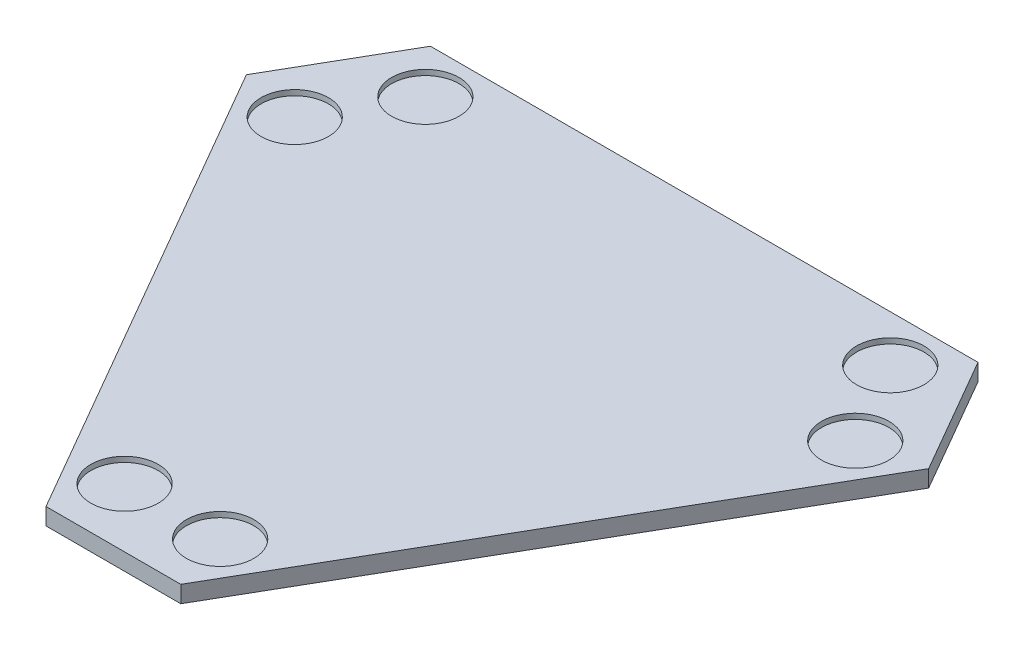
SolidWorks part; units mm, degrees
note: '?' marks a value the reader was unsure of. The reader was unsure of these and kept them because the rebuilt part matched: shared geometry of "Sketch1<5>".
ref_plane "Front Plane" through (0, 0, 0) normal (0, 0, 1) x (1, 0, 0)
ref_plane "Top Plane" through (0, 0, 0) normal (0, 1, 0) x (1, 0, 0)
ref_plane "Right Plane" through (0, 0, 0) normal (1, 0, 0) x (0, 0, -1)
sketch "Sketch1" plane through (0, 0, 0) normal (0, 1, 0) x (1, 0, 0)
  line L0 (121.2436, 70) -> (0, -140)
  line L1 (0, -140) -> (-121.2436, 70)
  line L2 (-121.2436, 70) -> (121.2436, 70)
  line L3 (121.2436, 70) -> (-60.6218, -35) construction
  line L4 (-121.2436, 70) -> (60.6218, -35) construction
  line L5 (-337.0463, -245.6128) -> (-234.4722, -67.9492)
  line L6 (-234.4722, -67.9492) -> (-131.898, -245.6128)
  line L7 (-131.898, -245.6128) -> (-337.0463, -245.6128)
  line L8 (-337.0463, -245.6128) -> (-183.1851, -156.781) construction
  line L9 (-131.898, -245.6128) -> (-285.7592, -156.781) construction
  line L10 (-182.4871, -105.359) -> (0, 210.718)
  line L11 (0, 210.718) -> (182.4871, -105.359)
  line L12 (182.4871, -105.359) -> (-182.4871, -105.359)
  line L13 (-182.4871, -105.359) -> (91.2436, 52.6795) construction
  line L14 (182.4871, -105.359) -> (-91.2436, 52.6795) construction
  line L15 (-30.1036, -87.859) -> (0, -87.859) construction
  line L16 (0, 70) -> (0, -140) construction
  line L18 (-96.883, 27.8062) -> (0, 27.8062) construction
  circle A0 centre (0, 0) radius 70 construction
  circle A1 centre (-14.187, -87.859) radius 10
  circle A2 centre (14.187, -87.859) radius 10
  point P21 (20, -105.359)
  point P24 (-20, -105.359)
  point P25 (-27.2169, -69.4629)
  dimension "D1" = 140
  dimension "D3" = 20
  dimension "D2" = 40
  dimension "D4" = 17.5
extrude "Boss-Extrude1" add sketch "Sketch1" along normal blind 5 contours L12 L0 L11 L2 L10 L1
extrude "Cut-Extrude4" cut sketch "Sketch1<5>" against normal blind 1.6 from surface at 5 starting at face at (0, 5, 0)
sketch "Sketch1<5>" plane through (0, 0, 0) normal (0, 1, 0) x (1, 0, 0) same geometry as "Sketch1"
sketch "Sketch3" plane through (0, 0, 0) normal (0, 0, 1) x (1, 0, 0)
  line L0 (0, 0) -> (0, 22.4752) construction
pattern_circular "CirPattern1" count 3 over 360 about axis through (0, 0, 0) along (0, 1, 0) of "Cut-Extrude4"
ref_axis "Axis1" through (0, -159.0727, 0) along (0, 1, 0)?
